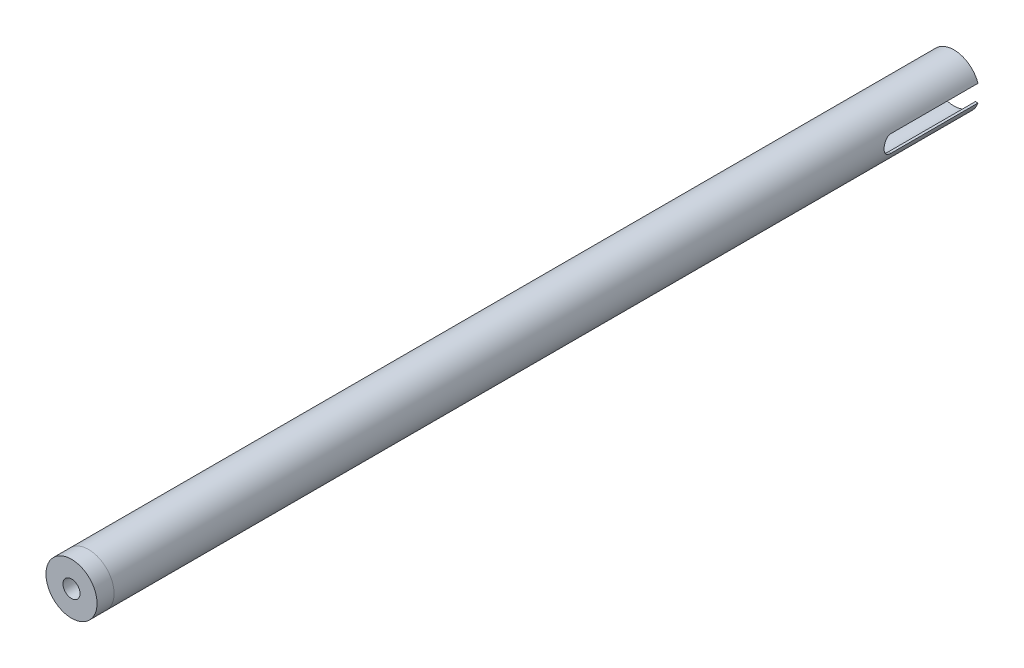
SolidWorks part; units mm, degrees
material "AISI 4130 Steel, normalized at 870C"
ref_plane "Front Plane" through (0, 0, 0) normal (0, 0, 1) x (1, 0, 0)
ref_plane "Top Plane" through (0, 0, 0) normal (0, 1, 0) x (1, 0, 0)
ref_plane "Right Plane" through (0, 0, 0) normal (1, 0, 0) x (0, 0, -1)
sketch "Axis" plane through (0, 0, 0) normal (0, 1, 0) x (1, 0, 0)
  line L0 (0, 0) -> (0, 329.0571) construction
  line L1 (0, 0) -> (0, -21.9075) construction
  line L2 (0, 329.0571) -> (-9.525, 329.0571) construction
  line L3 (0, 363.141) -> (-23.5893, 278.7301) construction
  dimension "D1" = 21.9075
  dimension "D2" = 9.525
sketch "Sketch1" plane through (0, 0, 0) normal (0, 0, 1) x (1, 0, 0)
  line L0 (-9.525, 0) -> (9.525, 0) construction
  line L1 (-8.9803, 3.175) -> (8.9803, 3.175)
  line L2 (-8.9803, -3.175) -> (8.9803, -3.175)
  circle A0 centre (0, 0) radius 9.525
  circle A1 centre (0, 0) radius 8.636
  circle A2 centre (0, 0) radius 3.175
  dimension "D1" = 19.05
  dimension "D3" = 6.35
  dimension "D2" = 0.889
  dimension "D4" = 6.35
extrude "Threaded insert 1-1" add sketch "Sketch1" against normal blind 6.35 contours A2 L1 A1 | A1 L1 A0 | A2 L0 A1 L1 | A1 L0 A0 L1 | L0 A1 L2 A0 | L0 A2 L2 A1 | A2 L2 A1 | A1 L2 A0 | L0 A1 L2 A2 | L0 A0 L2 A1 | A0 L0 A1 L1 | A1 L0 A2 L1 region at (5.4259, 1.6615, 0) region at (5.4259, -1.6615, 0) region at (8.8881, 1.6046, 0) region at (8.8881, -1.6046, 0) region at (-5.4259, -1.6615, 0) region at (-5.4259, 1.6615, 0) region at (0, 5.4321, 0) region at (0, -5.4321, 0) region at (0, 8.8265, 0) region at (8.5057, -3.3655, 0) region at (-8.8881, -1.6046, 0) region at (-8.8881, 1.6046, 0)
extrude "Threaded insert 1-2" add sketch "Sketch1<3>" against normal blind 6.35 from surface contours A2 L1 A1 | A2 L0 A1 L1 | L0 A2 L2 A1 | A2 L2 A1 | L0 A1 L2 A2 | A1 L0 A2 L1 region at (5.4259, 1.6615, 0) region at (5.4259, -1.6615, 0) region at (-5.4259, -1.6615, 0) region at (-5.4259, 1.6615, 0) region at (0, 5.4321, 0) region at (0, -5.4321, 0) starting at face at (9.525, 0, -6.35)
sketch "Sketch1<3>" plane through (0, 0, 0) normal (0, 0, 1) x (1, 0, 0) same geometry as "Sketch1"
extrude "A-arm tube" add sketch "Sketch1<4>" against normal up to vertex (329.0571 mm away) from surface separate body contours A1 L1 A0 | A1 L0 A0 L1 | L0 A1 L2 A0 | A1 L2 A0 | L0 A0 L2 A1 | A0 L0 A1 L1 region at (8.8881, 1.6046, 0) region at (8.8881, -1.6046, 0) region at (0, 8.8265, 0) region at (8.5057, -3.3655, 0) region at (-8.8881, -1.6046, 0) region at (-8.8881, 1.6046, 0) up to point (0, 0, -329.0571) starting at face at (8.636, 0, -6.35)
sketch "Sketch1<4>" plane through (0, 0, 0) normal (0, 0, 1) x (1, 0, 0) same geometry as "Sketch1"
extrude "Apex slot" cut sketch "Sketch1<5>" along normal blind 35.56 from surface contours A0 L0 A1 L1 | L0 A0 L2 A1 | A1 L0 A0 L1 | L0 A1 L2 A0 region at (8.8881, 1.6046, 0) region at (8.8881, -1.6046, 0) region at (-8.8881, -1.6046, 0) region at (-8.8881, 1.6046, 0) starting at face at (8.636, 0, -329.0571)
sketch "Sketch1<5>" plane through (0, 0, 0) normal (0, 0, 1) x (1, 0, 0) same geometry as "Sketch1"
fillet "Fillet1" radius 3.175 4 edges at (-8.5057, 3.175, -293.4971) (-8.5057, -3.175, -293.4971) (8.5057, -3.175, -293.4971) (8.5057, 3.175, -293.4971)
equation "\"tube diameter\"= 3 / 4"
equation "\"tube thickness\"= .035"
equation "\"apex thickness\"= .25"
equation "\"tube slot\"= 1.4"
equation "\"D1@Sketch1\"=\"tube diameter\""
equation "\"D2@Sketch1\"=\"tube thickness\""
equation "\"threaded insert hole\"= 1 / 4"
equation "\"D3@Sketch1\"=\"threaded insert hole\""
equation "\"D4@Sketch1\"=\"apex thickness\""
equation "\"D1@Apex slot\" = \"tube slot\""
equation "\"D1@Fillet1\"=\"apex thickness\"/2"
equation "\"D2@Axis\"=\"tube diameter\"/2"
